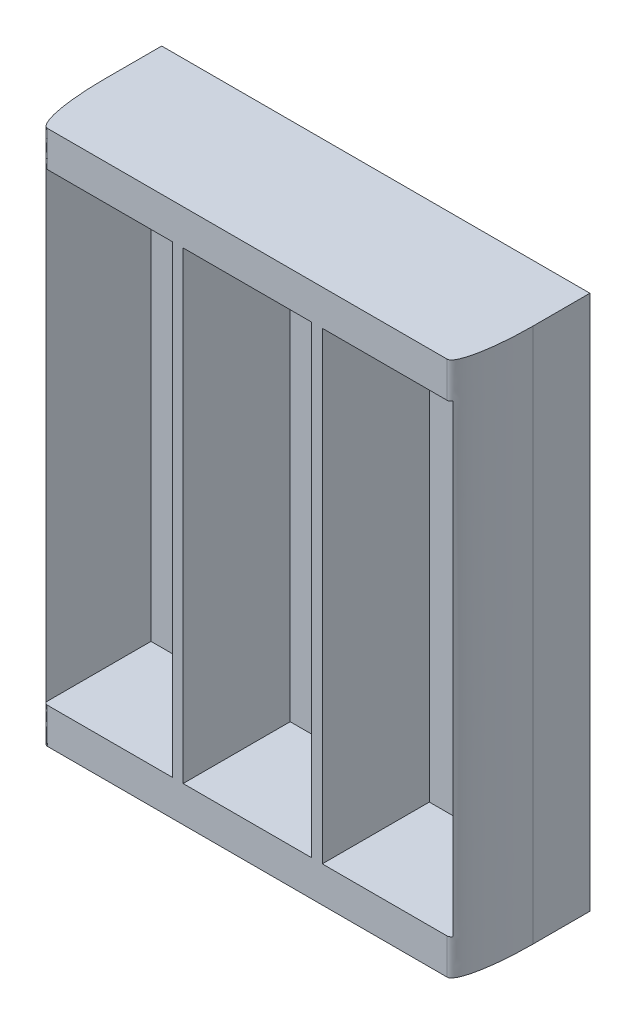
SolidWorks part; units mm, degrees
ref_plane "Front Plane" through (0, 0, 0) normal (0, 0, 1) x (1, 0, 0)
ref_plane "Top Plane" through (0, 0, 0) normal (0, 1, 0) x (1, 0, 0)
ref_plane "Right Plane" through (0, 0, 0) normal (1, 0, 0) x (0, 0, -1)
sketch "Sketch1" plane through (0, 0, 0) normal (0, 1, 0) x (1, 0, 0)
  line L0 (-30, 0) -> (30, 0)
  line L1 (-30, 0) -> (-30, -18)
  line L2 (-30, -18) -> (30, -18)
  line L3 (30, -18) -> (30, 0)
  point P4 (0, 0)
  dimension "D1" = 60
  dimension "D2" = 18
extrude "Boss-Extrude1" add sketch "Sketch1" along normal blind 75
sketch "Sketch2" plane through (0, 0, 18) normal (0, 0, 1) x (1, 0, 0)
  line L0 (-30, 0) -> (30, 0) construction
  line L1 (-28.5, 70) -> (-10.5, 70)
  line L2 (-28.5, 70) -> (-28.5, 5)
  line L3 (-28.5, 5) -> (-10.5, 5)
  line L4 (-10.5, 70) -> (-10.5, 5)
  line L5 (-30, 75) -> (-30, 0) construction
  line L6 (-9, 70) -> (-9, 5)
  line L7 (-9, 70) -> (9, 70)
  line L8 (9, 70) -> (9, 5)
  line L9 (-9, 5) -> (9, 5)
  line L10 (10.5, 70) -> (10.5, 5)
  line L11 (10.5, 70) -> (28.5, 70)
  line L12 (28.5, 70) -> (28.5, 5)
  line L13 (10.5, 5) -> (28.5, 5)
  dimension "D1" = 18
  dimension "D2" = 65
  dimension "D3" = 5
  dimension "D4" = 1.5
  dimension "D5" = 3
extrude "Cut-Extrude1" cut sketch "Sketch2" against normal blind 15
fillet "Fillet1" radius 10 2 edges at (-30, 37.5, 18) (30, 37.5, 18)
